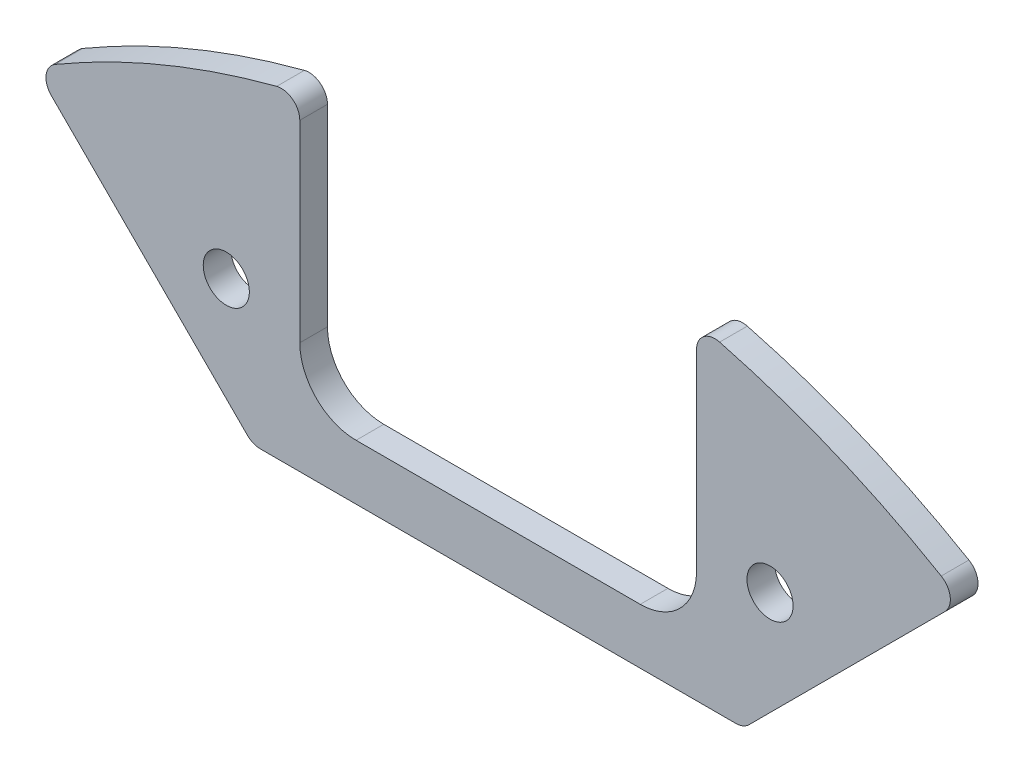
SolidWorks part; units mm, degrees
material "5052-H34"
ref_plane "正面" through (0, 0, 0) normal (0, 0, 1) x (1, 0, 0)
ref_plane "平面" through (0, 0, 0) normal (0, 1, 0) x (1, 0, 0)
ref_plane "右側面" through (0, 0, 0) normal (1, 0, 0) x (0, 0, -1)
sketch "ｽｹｯﾁ1" plane through (0, 0, 0) normal (0, 0, 1) x (1, 0, 0)
  circle A0 centre (0, 0) radius 47.5
  dimension "D1" = 95
extrude "ﾎﾞｽ - 押し出し1" add sketch "ｽｹｯﾁ1" along normal blind 1.5
sketch "ｽｹｯﾁ2" plane through (0, 0, 1.5) normal (0, 0, 1) x (1, 0, 0)
  line L0 (0, 0) -> (0, 47.5) construction
  line L1 (-10.75, 43.525) -> (-10.75, 52.5)
  line L2 (-10.75, 31.5) -> (10.75, 31.5)
  line L3 (-10.75, 31.5) -> (-10.75, 40.475)
  line L4 (-10.75, 52.5) -> (10.75, 52.5)
  line L5 (10.75, 31.5) -> (10.75, 40.475)
  line L6 (-10.75, 31.5) -> (10.75, 52.5) construction
  line L7 (-10.75, 52.5) -> (10.75, 31.5) construction
  line L8 (-13, 43.525) -> (-10.75, 43.525)
  line L9 (-13, 43.525) -> (-13, 40.475)
  line L10 (-13, 40.475) -> (-10.75, 40.475)
  line L11 (13, 43.525) -> (13, 40.475)
  line L12 (-13, 43.525) -> (13, 40.475) construction
  line L13 (-13, 40.475) -> (13, 43.525) construction
  line L14 (10.75, 43.525) -> (10.75, 52.5)
  line L15 (10.75, 43.525) -> (13, 43.525)
  line L17 (10.75, 40.475) -> (13, 40.475)
  circle A0 centre (0, 0) radius 47.5 construction
  point P5 (0, 42)
  point P10 (0, 42)
  dimension "D1" = 42
  dimension "D2" = 21.5
  dimension "D3" = 21
  dimension "D4" = 3.05
  dimension "D5" = 26
extrude "ｶｯﾄ - 押し出し1" cut sketch "ｽｹｯﾁ2" against normal through all
sketch "ｽｹｯﾁ3" plane through (0, 0, 1.5) normal (0, 0, 1) x (1, 0, 0)
  line L1 (-8.8388, -8.8388) -> (8.8388, -8.8388) construction
  line L2 (-8.8388, -8.8388) -> (-8.8388, 8.8388) construction
  line L3 (-8.8388, 8.8388) -> (8.8388, 8.8388) construction
  line L4 (8.8388, -8.8388) -> (8.8388, 8.8388) construction
  line L5 (-8.8388, -8.8388) -> (8.8388, 8.8388) construction
  line L6 (-8.8388, 8.8388) -> (8.8388, -8.8388) construction
  circle A0 centre (0, 0) radius 3.1
  circle A1 centre (0, 0) radius 6.5 construction
  circle A2 centre (0, 6.5) radius 1.6
  circle A3 centre (6.5, 0) radius 1.6
  circle A4 centre (0, -6.5) radius 1.6
  circle A5 centre (-6.5, 0) radius 1.6
  circle A6 centre (0, 0) radius 12.5 construction
  circle A7 centre (8.8388, 8.8388) radius 1.6
  circle A8 centre (8.8388, -8.8388) radius 1.6
  circle A9 centre (-8.8388, -8.8388) radius 1.6
  circle A10 centre (-8.8388, 8.8388) radius 1.6
  dimension "D1" = 6.2
  dimension "D2" = 13
  dimension "D3" = 3.2
  dimension "D5" = 25
  dimension "D6" = 3.2
  dimension "D4" = 4
  dimension "D7" = 4
extrude "ｶｯﾄ - 押し出し2" cut sketch "ｽｹｯﾁ3" against normal through all and the other way through all
sketch "ｽｹｯﾁ4" plane through (0, 0, 1.5) normal (0, 0, 1) x (1, 0, 0)
  line L0 (0, 31.5) -> (0, 0) construction
  line L1 (-10.75, 31.5) -> (10.75, 31.5) construction
  line L2 (0, 0) -> (14.7333, 35.5694) construction
  circle A0 centre (0, 0) radius 22.5 construction
  circle A1 centre (0, 0) radius 38.5 construction
  circle A2 centre (14.7333, 35.5694) radius 1.25
  circle A3 centre (8.6104, 20.7873) radius 1.25
  dimension "D1" = 45
  dimension "D2" = 77
  dimension "D4" = 2.5
  dimension "D3" = 22.5
extrude "ｶｯﾄ - 押し出し3" cut sketch "ｽｹｯﾁ4" against normal through all
sketch "ｽｹｯﾁ5" plane through (0, 0, 1.5) normal (0, 0, 1) x (1, 0, 0)
  line L0 (0, 0) -> (14.7333, 35.5694) construction
  line L1 (-10.75, 31.5) -> (10.75, 31.5) construction
  line L2 (-10.75, 31.5) -> (10.75, 31.5) construction
  line L3 (-7.1883, 26.5) -> (7.1883, 26.5)
  line L4 (-3.3281, 17.1806) -> (-7.1883, 26.5)
  line L5 (0, 31.5) -> (0, 0) construction
  line L6 (-10.75, 26.5) -> (10.75, 26.5) construction
  line L9 (-3.3281, 17.1806) -> (3.3281, 17.1806)
  line L10 (3.3281, 17.1806) -> (7.1883, 26.5)
  circle A0 centre (0, 0) radius 17.5 construction
  dimension "D3" = 35
  dimension "D2" = 7
  dimension "D1" = 5
extrude "ｶｯﾄ - 押し出し4" cut sketch "ｽｹｯﾁ5" against normal through all and the other way through all
fillet "ﾌｨﾚｯﾄ1" radius 1 6 edges at (-3.3281, 17.1806, 0.75) (3.3281, 17.1806, 0.75) (7.1883, 26.5, 0.75) (-7.1883, 26.5, 0.75) (10.75, 46.2676, 0.75) (-10.75, 46.2676, 0.75)
fillet "ﾌｨﾚｯﾄ2" radius 0.2 4 edges at (13, 43.525, 0.75) (13, 40.475, 0.75) (-13, 43.525, 0.75) (-13, 40.475, 0.75)
fillet "ﾌｨﾚｯﾄ3" radius 3.05 2 edges at (10.75, 31.5, 0.75) (-10.75, 31.5, 0.75)
ref_axis "軸1" through (0, 0, 0) along (0, 0, 1)
pattern_circular "円形ﾊﾟﾀｰﾝ1" count 8 over 360 about axis through (0, 0, 0) along (0, 0, 1) of "ｶｯﾄ - 押し出し1", "ﾌｨﾚｯﾄ1", "ｶｯﾄ - 押し出し4", "ｶｯﾄ - 押し出し3", "ﾌｨﾚｯﾄ2", "ﾌｨﾚｯﾄ3"
sketch "ｽｹｯﾁ6" plane through (0, 0, 1.5) normal (0, 0, 1) x (1, 0, 0)
  line L0 (7.7, 28.5) -> (-7.7, 28.5)
  line L1 (-7.7, 28.5) -> (-13.2972, 28.5)
  line L2 (-13.2972, 28.5) -> (-21.0187, 36.2215)
  line L3 (7.7, 28.5) -> (13.2972, 28.5)
  line L4 (25.5973, 14.7078) -> (14.7078, 25.5973)
  line L7 (28.5, -7.7) -> (28.5, 7.7)
  line L10 (14.7078, -25.5973) -> (25.5973, -14.7078)
  line L13 (-7.7, -28.5) -> (7.7, -28.5)
  line L16 (-25.5973, -14.7078) -> (-14.7078, -25.5973)
  line L19 (-28.5, 7.7) -> (-28.5, -7.7)
  line L22 (-14.7078, 25.5973) -> (-25.5973, 14.7078)
  line L23 (13.2972, 28.5) -> (21.0187, 36.2215)
  line L88 (39.4148, 24.212) -> (38.3782, 23.1754)
  line L89 (38.3782, 23.1754) -> (39.8278, 21.7259)
  line L90 (39.8278, 21.443) -> (37.954, 19.5692)
  line L91 (37.6711, 19.5692) -> (36.2215, 21.0187)
  line L92 (36.2215, 21.0187) -> (32.0319, 16.8291)
  line L93 (27.7186, 16.8291) -> (16.8291, 27.7186)
  line L94 (16.8291, 32.0319) -> (21.0187, 36.2215)
  line L95 (21.0187, 36.2215) -> (19.5692, 37.6711)
  line L96 (19.5692, 37.954) -> (21.443, 39.8278)
  line L97 (21.7259, 39.8278) -> (23.1754, 38.3782)
  line L98 (23.1754, 38.3782) -> (24.212, 39.4148)
  line L99 (10.75, 44.991) -> (10.75, 43.525)
  line L100 (10.75, 43.525) -> (12.8, 43.525)
  line L101 (13, 43.325) -> (13, 40.675)
  line L102 (12.8, 40.475) -> (10.75, 40.475)
  line L103 (10.75, 40.475) -> (10.75, 34.55)
  line L104 (7.7, 31.5) -> (-7.7, 31.5)
  line L105 (-10.75, 34.55) -> (-10.75, 40.475)
  line L106 (-10.75, 40.475) -> (-12.8, 40.475)
  line L107 (-13, 40.675) -> (-13, 43.325)
  line L108 (-12.8, 43.525) -> (-10.75, 43.525)
  line L109 (-10.75, 43.525) -> (-10.75, 44.991)
  line L110 (-24.212, 39.4148) -> (-23.1754, 38.3782)
  line L111 (-23.1754, 38.3782) -> (-21.7259, 39.8278)
  line L112 (-21.443, 39.8278) -> (-19.5692, 37.954)
  line L113 (-19.5692, 37.6711) -> (-21.0187, 36.2215)
  line L114 (-21.0187, 36.2215) -> (-16.8291, 32.0319)
  line L115 (-16.8291, 27.7186) -> (-27.7186, 16.8291)
  line L116 (-32.0319, 16.8291) -> (-36.2215, 21.0187)
  line L117 (-36.2215, 21.0187) -> (-37.6711, 19.5692)
  line L118 (-37.954, 19.5692) -> (-39.8278, 21.443)
  line L119 (-39.8278, 21.7259) -> (-38.3782, 23.1754)
  line L120 (-38.3782, 23.1754) -> (-39.4148, 24.212)
  line L121 (-44.991, 10.75) -> (-43.525, 10.75)
  line L122 (-43.525, 10.75) -> (-43.525, 12.8)
  line L123 (-43.325, 13) -> (-40.675, 13)
  line L124 (-40.475, 12.8) -> (-40.475, 10.75)
  line L125 (-40.475, 10.75) -> (-34.55, 10.75)
  line L126 (-31.5, 7.7) -> (-31.5, -7.7)
  line L127 (-34.55, -10.75) -> (-40.475, -10.75)
  line L128 (-40.475, -10.75) -> (-40.475, -12.8)
  line L129 (-40.675, -13) -> (-43.325, -13)
  line L130 (-43.525, -12.8) -> (-43.525, -10.75)
  line L131 (-43.525, -10.75) -> (-44.991, -10.75)
  line L132 (-39.4148, -24.212) -> (-38.3782, -23.1754)
  line L133 (-38.3782, -23.1754) -> (-39.8278, -21.7259)
  line L134 (-39.8278, -21.443) -> (-37.954, -19.5692)
  line L135 (-37.6711, -19.5692) -> (-36.2215, -21.0187)
  line L136 (-36.2215, -21.0187) -> (-32.0319, -16.8291)
  line L137 (-27.7186, -16.8291) -> (-16.8291, -27.7186)
  line L138 (-16.8291, -32.0319) -> (-21.0187, -36.2215)
  line L139 (-21.0187, -36.2215) -> (-19.5692, -37.6711)
  line L140 (-19.5692, -37.954) -> (-21.443, -39.8278)
  line L141 (-21.7259, -39.8278) -> (-23.1754, -38.3782)
  line L142 (-23.1754, -38.3782) -> (-24.212, -39.4148)
  line L143 (-10.75, -44.991) -> (-10.75, -43.525)
  line L144 (-10.75, -43.525) -> (-12.8, -43.525)
  line L145 (-13, -43.325) -> (-13, -40.675)
  line L146 (-12.8, -40.475) -> (-10.75, -40.475)
  line L147 (-10.75, -40.475) -> (-10.75, -34.55)
  line L148 (-7.7, -31.5) -> (7.7, -31.5)
  line L149 (10.75, -34.55) -> (10.75, -40.475)
  line L150 (10.75, -40.475) -> (12.8, -40.475)
  line L151 (13, -40.675) -> (13, -43.325)
  line L152 (12.8, -43.525) -> (10.75, -43.525)
  line L153 (10.75, -43.525) -> (10.75, -44.991)
  line L154 (24.212, -39.4148) -> (23.1754, -38.3782)
  line L155 (23.1754, -38.3782) -> (21.7259, -39.8278)
  line L156 (21.443, -39.8278) -> (19.5692, -37.954)
  line L157 (19.5692, -37.6711) -> (21.0187, -36.2215)
  line L158 (21.0187, -36.2215) -> (16.8291, -32.0319)
  line L159 (16.8291, -27.7186) -> (27.7186, -16.8291)
  line L160 (32.0319, -16.8291) -> (36.2215, -21.0187)
  line L161 (36.2215, -21.0187) -> (37.6711, -19.5692)
  line L162 (37.954, -19.5692) -> (39.8278, -21.443)
  line L163 (39.8278, -21.7259) -> (38.3782, -23.1754)
  line L164 (38.3782, -23.1754) -> (39.4148, -24.212)
  line L165 (44.991, -10.75) -> (43.525, -10.75)
  line L166 (43.525, -10.75) -> (43.525, -12.8)
  line L167 (43.325, -13) -> (40.675, -13)
  line L168 (40.475, -12.8) -> (40.475, -10.75)
  line L169 (40.475, -10.75) -> (34.55, -10.75)
  line L170 (31.5, -7.7) -> (31.5, 7.7)
  line L171 (34.55, 10.75) -> (40.475, 10.75)
  line L172 (40.475, 10.75) -> (40.475, 12.8)
  line L173 (40.675, 13) -> (43.325, 13)
  line L174 (43.525, 12.8) -> (43.525, 10.75)
  line L175 (43.525, 10.75) -> (44.991, 10.75)
  line L176 (39.4148, 24.212) -> (38.3782, 23.1754)
  line L177 (38.3782, 23.1754) -> (39.8278, 21.7259)
  line L178 (39.8278, 21.443) -> (37.954, 19.5692)
  line L179 (37.6711, 19.5692) -> (36.2215, 21.0187)
  line L180 (36.2215, 21.0187) -> (32.0319, 16.8291)
  line L181 (27.7186, 16.8291) -> (16.8291, 27.7186)
  line L182 (16.8291, 32.0319) -> (21.0187, 36.2215)
  line L183 (21.0187, 36.2215) -> (19.5692, 37.6711)
  line L184 (19.5692, 37.954) -> (21.443, 39.8278)
  line L185 (21.7259, 39.8278) -> (23.1754, 38.3782)
  line L186 (23.1754, 38.3782) -> (24.212, 39.4148)
  line L187 (10.75, 44.991) -> (10.75, 43.525)
  line L188 (10.75, 43.525) -> (12.8, 43.525)
  line L189 (13, 43.325) -> (13, 40.675)
  line L190 (12.8, 40.475) -> (10.75, 40.475)
  line L191 (10.75, 40.475) -> (10.75, 34.55)
  line L192 (7.7, 31.5) -> (-7.7, 31.5)
  line L193 (-10.75, 34.55) -> (-10.75, 40.475)
  line L194 (-10.75, 40.475) -> (-12.8, 40.475)
  line L195 (-13, 40.675) -> (-13, 43.325)
  line L196 (-12.8, 43.525) -> (-10.75, 43.525)
  line L197 (-10.75, 43.525) -> (-10.75, 44.991)
  line L198 (-24.212, 39.4148) -> (-23.1754, 38.3782)
  line L199 (-23.1754, 38.3782) -> (-21.7259, 39.8278)
  line L200 (-21.443, 39.8278) -> (-19.5692, 37.954)
  line L201 (-19.5692, 37.6711) -> (-21.0187, 36.2215)
  line L202 (-21.0187, 36.2215) -> (-16.8291, 32.0319)
  line L203 (-16.8291, 27.7186) -> (-27.7186, 16.8291)
  line L204 (-32.0319, 16.8291) -> (-36.2215, 21.0187)
  line L205 (-36.2215, 21.0187) -> (-37.6711, 19.5692)
  line L206 (-37.954, 19.5692) -> (-39.8278, 21.443)
  line L207 (-39.8278, 21.7259) -> (-38.3782, 23.1754)
  line L208 (-38.3782, 23.1754) -> (-39.4148, 24.212)
  line L209 (-44.991, 10.75) -> (-43.525, 10.75)
  line L210 (-43.525, 10.75) -> (-43.525, 12.8)
  line L211 (-43.325, 13) -> (-40.675, 13)
  line L212 (-40.475, 12.8) -> (-40.475, 10.75)
  line L213 (-40.475, 10.75) -> (-34.55, 10.75)
  line L214 (-31.5, 7.7) -> (-31.5, -7.7)
  line L215 (-34.55, -10.75) -> (-40.475, -10.75)
  line L216 (-40.475, -10.75) -> (-40.475, -12.8)
  line L217 (-40.675, -13) -> (-43.325, -13)
  line L218 (-43.525, -12.8) -> (-43.525, -10.75)
  line L219 (-43.525, -10.75) -> (-44.991, -10.75)
  line L220 (-39.4148, -24.212) -> (-38.3782, -23.1754)
  line L221 (-38.3782, -23.1754) -> (-39.8278, -21.7259)
  line L222 (-39.8278, -21.443) -> (-37.954, -19.5692)
  line L223 (-37.6711, -19.5692) -> (-36.2215, -21.0187)
  line L224 (-36.2215, -21.0187) -> (-32.0319, -16.8291)
  line L225 (-27.7186, -16.8291) -> (-16.8291, -27.7186)
  line L226 (-16.8291, -32.0319) -> (-21.0187, -36.2215)
  line L227 (-21.0187, -36.2215) -> (-19.5692, -37.6711)
  line L228 (-19.5692, -37.954) -> (-21.443, -39.8278)
  line L229 (-21.7259, -39.8278) -> (-23.1754, -38.3782)
  line L230 (-23.1754, -38.3782) -> (-24.212, -39.4148)
  line L231 (-10.75, -44.991) -> (-10.75, -43.525)
  line L232 (-10.75, -43.525) -> (-12.8, -43.525)
  line L233 (-13, -43.325) -> (-13, -40.675)
  line L234 (-12.8, -40.475) -> (-10.75, -40.475)
  line L235 (-10.75, -40.475) -> (-10.75, -34.55)
  line L236 (-7.7, -31.5) -> (7.7, -31.5)
  line L237 (10.75, -34.55) -> (10.75, -40.475)
  line L238 (10.75, -40.475) -> (12.8, -40.475)
  line L239 (13, -40.675) -> (13, -43.325)
  line L240 (12.8, -43.525) -> (10.75, -43.525)
  line L241 (10.75, -43.525) -> (10.75, -44.991)
  line L242 (24.212, -39.4148) -> (23.1754, -38.3782)
  line L243 (23.1754, -38.3782) -> (21.7259, -39.8278)
  line L244 (21.443, -39.8278) -> (19.5692, -37.954)
  line L245 (19.5692, -37.6711) -> (21.0187, -36.2215)
  line L246 (21.0187, -36.2215) -> (16.8291, -32.0319)
  line L247 (16.8291, -27.7186) -> (27.7186, -16.8291)
  line L248 (32.0319, -16.8291) -> (36.2215, -21.0187)
  line L249 (36.2215, -21.0187) -> (37.6711, -19.5692)
  line L250 (37.954, -19.5692) -> (39.8278, -21.443)
  line L251 (39.8278, -21.7259) -> (38.3782, -23.1754)
  line L252 (38.3782, -23.1754) -> (39.4148, -24.212)
  line L253 (44.991, -10.75) -> (43.525, -10.75)
  line L254 (43.525, -10.75) -> (43.525, -12.8)
  line L255 (43.325, -13) -> (40.675, -13)
  line L256 (40.475, -12.8) -> (40.475, -10.75)
  line L257 (40.475, -10.75) -> (34.55, -10.75)
  line L258 (31.5, -7.7) -> (31.5, 7.7)
  line L259 (34.55, 10.75) -> (40.475, 10.75)
  line L260 (40.475, 10.75) -> (40.475, 12.8)
  line L261 (40.675, 13) -> (43.325, 13)
  line L262 (43.525, 12.8) -> (43.525, 10.75)
  line L263 (43.525, 10.75) -> (44.991, 10.75)
  arc A72 (45.9585, 12.0027) -> (40.9848, 24.0104) centre (0, 0) ccw
  arc A73 (40.9848, 24.0104) -> (39.4148, 24.212) centre (40.1219, 23.5049) ccw
  arc A74 (39.8278, 21.443) -> (39.8278, 21.7259) centre (39.6864, 21.5844) ccw
  arc A75 (37.6711, 19.5692) -> (37.954, 19.5692) centre (37.8125, 19.7106) ccw
  arc A76 (27.7186, 16.8291) -> (32.0319, 16.8291) centre (29.8753, 18.9858) ccw
  arc A77 (16.8291, 32.0319) -> (16.8291, 27.7186) centre (18.9858, 29.8753) ccw
  arc A78 (19.5692, 37.954) -> (19.5692, 37.6711) centre (19.7106, 37.8125) ccw
  arc A79 (21.7259, 39.8278) -> (21.443, 39.8278) centre (21.5844, 39.6864) ccw
  arc A80 (24.212, 39.4148) -> (24.0104, 40.9848) centre (23.5049, 40.1219) ccw
  arc A81 (24.0104, 40.9848) -> (12.0027, 45.9585) centre (0, 0) ccw
  arc A82 (12.0027, 45.9585) -> (10.75, 44.991) centre (11.75, 44.991) ccw
  arc A83 (13, 43.325) -> (12.8, 43.525) centre (12.8, 43.325) ccw
  arc A84 (12.8, 40.475) -> (13, 40.675) centre (12.8, 40.675) ccw
  arc A85 (7.7, 31.5) -> (10.75, 34.55) centre (7.7, 34.55) ccw
  arc A86 (-10.75, 34.55) -> (-7.7, 31.5) centre (-7.7, 34.55) ccw
  arc A87 (-13, 40.675) -> (-12.8, 40.475) centre (-12.8, 40.675) ccw
  arc A88 (-12.8, 43.525) -> (-13, 43.325) centre (-12.8, 43.325) ccw
  arc A89 (-10.75, 44.991) -> (-12.0027, 45.9585) centre (-11.75, 44.991) ccw
  arc A90 (-12.0027, 45.9585) -> (-24.0104, 40.9848) centre (0, 0) ccw
  arc A91 (-24.0104, 40.9848) -> (-24.212, 39.4148) centre (-23.5049, 40.1219) ccw
  arc A92 (-21.443, 39.8278) -> (-21.7259, 39.8278) centre (-21.5844, 39.6864) ccw
  arc A93 (-19.5692, 37.6711) -> (-19.5692, 37.954) centre (-19.7106, 37.8125) ccw
  arc A94 (-16.8291, 27.7186) -> (-16.8291, 32.0319) centre (-18.9858, 29.8753) ccw
  arc A95 (-32.0319, 16.8291) -> (-27.7186, 16.8291) centre (-29.8753, 18.9858) ccw
  arc A96 (-37.954, 19.5692) -> (-37.6711, 19.5692) centre (-37.8125, 19.7106) ccw
  arc A97 (-39.8278, 21.7259) -> (-39.8278, 21.443) centre (-39.6864, 21.5844) ccw
  arc A98 (-39.4148, 24.212) -> (-40.9848, 24.0104) centre (-40.1219, 23.5049) ccw
  arc A99 (-40.9848, 24.0104) -> (-45.9585, 12.0027) centre (0, 0) ccw
  arc A100 (-45.9585, 12.0027) -> (-44.991, 10.75) centre (-44.991, 11.75) ccw
  arc A101 (-43.325, 13) -> (-43.525, 12.8) centre (-43.325, 12.8) ccw
  arc A102 (-40.475, 12.8) -> (-40.675, 13) centre (-40.675, 12.8) ccw
  arc A103 (-31.5, 7.7) -> (-34.55, 10.75) centre (-34.55, 7.7) ccw
  arc A104 (-34.55, -10.75) -> (-31.5, -7.7) centre (-34.55, -7.7) ccw
  arc A105 (-40.675, -13) -> (-40.475, -12.8) centre (-40.675, -12.8) ccw
  arc A106 (-43.525, -12.8) -> (-43.325, -13) centre (-43.325, -12.8) ccw
  arc A107 (-44.991, -10.75) -> (-45.9585, -12.0027) centre (-44.991, -11.75) ccw
  arc A108 (-45.9585, -12.0027) -> (-40.9848, -24.0104) centre (0, 0) ccw
  arc A109 (-40.9848, -24.0104) -> (-39.4148, -24.212) centre (-40.1219, -23.5049) ccw
  arc A110 (-39.8278, -21.443) -> (-39.8278, -21.7259) centre (-39.6864, -21.5844) ccw
  arc A111 (-37.6711, -19.5692) -> (-37.954, -19.5692) centre (-37.8125, -19.7106) ccw
  arc A112 (-27.7186, -16.8291) -> (-32.0319, -16.8291) centre (-29.8753, -18.9858) ccw
  arc A113 (-16.8291, -32.0319) -> (-16.8291, -27.7186) centre (-18.9858, -29.8753) ccw
  arc A114 (-19.5692, -37.954) -> (-19.5692, -37.6711) centre (-19.7106, -37.8125) ccw
  arc A115 (-21.7259, -39.8278) -> (-21.443, -39.8278) centre (-21.5844, -39.6864) ccw
  arc A116 (-24.212, -39.4148) -> (-24.0104, -40.9848) centre (-23.5049, -40.1219) ccw
  arc A117 (-24.0104, -40.9848) -> (-12.0027, -45.9585) centre (0, 0) ccw
  arc A118 (-12.0027, -45.9585) -> (-10.75, -44.991) centre (-11.75, -44.991) ccw
  arc A119 (-13, -43.325) -> (-12.8, -43.525) centre (-12.8, -43.325) ccw
  arc A120 (-12.8, -40.475) -> (-13, -40.675) centre (-12.8, -40.675) ccw
  arc A121 (-7.7, -31.5) -> (-10.75, -34.55) centre (-7.7, -34.55) ccw
  arc A122 (10.75, -34.55) -> (7.7, -31.5) centre (7.7, -34.55) ccw
  arc A123 (13, -40.675) -> (12.8, -40.475) centre (12.8, -40.675) ccw
  arc A124 (12.8, -43.525) -> (13, -43.325) centre (12.8, -43.325) ccw
  arc A125 (10.75, -44.991) -> (12.0027, -45.9585) centre (11.75, -44.991) ccw
  arc A126 (12.0027, -45.9585) -> (24.0104, -40.9848) centre (0, 0) ccw
  arc A127 (24.0104, -40.9848) -> (24.212, -39.4148) centre (23.5049, -40.1219) ccw
  arc A128 (21.443, -39.8278) -> (21.7259, -39.8278) centre (21.5844, -39.6864) ccw
  arc A129 (19.5692, -37.6711) -> (19.5692, -37.954) centre (19.7106, -37.8125) ccw
  arc A130 (16.8291, -27.7186) -> (16.8291, -32.0319) centre (18.9858, -29.8753) ccw
  arc A131 (32.0319, -16.8291) -> (27.7186, -16.8291) centre (29.8753, -18.9858) ccw
  arc A132 (37.954, -19.5692) -> (37.6711, -19.5692) centre (37.8125, -19.7106) ccw
  arc A133 (39.8278, -21.7259) -> (39.8278, -21.443) centre (39.6864, -21.5844) ccw
  arc A134 (39.4148, -24.212) -> (40.9848, -24.0104) centre (40.1219, -23.5049) ccw
  arc A135 (40.9848, -24.0104) -> (45.9585, -12.0027) centre (0, 0) ccw
  arc A136 (45.9585, -12.0027) -> (44.991, -10.75) centre (44.991, -11.75) ccw
  arc A137 (43.325, -13) -> (43.525, -12.8) centre (43.325, -12.8) ccw
  arc A138 (40.475, -12.8) -> (40.675, -13) centre (40.675, -12.8) ccw
  arc A139 (31.5, -7.7) -> (34.55, -10.75) centre (34.55, -7.7) ccw
  arc A140 (34.55, 10.75) -> (31.5, 7.7) centre (34.55, 7.7) ccw
  arc A141 (40.675, 13) -> (40.475, 12.8) centre (40.675, 12.8) ccw
  arc A142 (43.525, 12.8) -> (43.325, 13) centre (43.325, 12.8) ccw
  arc A143 (44.991, 10.75) -> (45.9585, 12.0027) centre (44.991, 11.75) ccw
  arc A144 (45.9585, 12.0027) -> (40.9848, 24.0104) centre (0, 0) ccw
  arc A145 (40.9848, 24.0104) -> (39.4148, 24.212) centre (40.1219, 23.5049) ccw
  arc A146 (39.8278, 21.443) -> (39.8278, 21.7259) centre (39.6864, 21.5844) ccw
  arc A147 (37.6711, 19.5692) -> (37.954, 19.5692) centre (37.8125, 19.7106) ccw
  arc A148 (27.7186, 16.8291) -> (32.0319, 16.8291) centre (29.8753, 18.9858) ccw
  arc A149 (16.8291, 32.0319) -> (16.8291, 27.7186) centre (18.9858, 29.8753) ccw
  arc A150 (19.5692, 37.954) -> (19.5692, 37.6711) centre (19.7106, 37.8125) ccw
  arc A151 (21.7259, 39.8278) -> (21.443, 39.8278) centre (21.5844, 39.6864) ccw
  arc A152 (24.212, 39.4148) -> (24.0104, 40.9848) centre (23.5049, 40.1219) ccw
  arc A153 (24.0104, 40.9848) -> (12.0027, 45.9585) centre (0, 0) ccw
  arc A154 (12.0027, 45.9585) -> (10.75, 44.991) centre (11.75, 44.991) ccw
  arc A155 (13, 43.325) -> (12.8, 43.525) centre (12.8, 43.325) ccw
  arc A156 (12.8, 40.475) -> (13, 40.675) centre (12.8, 40.675) ccw
  arc A157 (7.7, 31.5) -> (10.75, 34.55) centre (7.7, 34.55) ccw
  arc A158 (-10.75, 34.55) -> (-7.7, 31.5) centre (-7.7, 34.55) ccw
  arc A159 (-13, 40.675) -> (-12.8, 40.475) centre (-12.8, 40.675) ccw
  arc A160 (-12.8, 43.525) -> (-13, 43.325) centre (-12.8, 43.325) ccw
  arc A161 (-10.75, 44.991) -> (-12.0027, 45.9585) centre (-11.75, 44.991) ccw
  arc A162 (-12.0027, 45.9585) -> (-24.0104, 40.9848) centre (0, 0) ccw
  arc A163 (-24.0104, 40.9848) -> (-24.212, 39.4148) centre (-23.5049, 40.1219) ccw
  arc A164 (-21.443, 39.8278) -> (-21.7259, 39.8278) centre (-21.5844, 39.6864) ccw
  arc A165 (-19.5692, 37.6711) -> (-19.5692, 37.954) centre (-19.7106, 37.8125) ccw
  arc A166 (-16.8291, 27.7186) -> (-16.8291, 32.0319) centre (-18.9858, 29.8753) ccw
  arc A167 (-32.0319, 16.8291) -> (-27.7186, 16.8291) centre (-29.8753, 18.9858) ccw
  arc A168 (-37.954, 19.5692) -> (-37.6711, 19.5692) centre (-37.8125, 19.7106) ccw
  arc A169 (-39.8278, 21.7259) -> (-39.8278, 21.443) centre (-39.6864, 21.5844) ccw
  arc A170 (-39.4148, 24.212) -> (-40.9848, 24.0104) centre (-40.1219, 23.5049) ccw
  arc A171 (-40.9848, 24.0104) -> (-45.9585, 12.0027) centre (0, 0) ccw
  arc A172 (-45.9585, 12.0027) -> (-44.991, 10.75) centre (-44.991, 11.75) ccw
  arc A173 (-43.325, 13) -> (-43.525, 12.8) centre (-43.325, 12.8) ccw
  arc A174 (-40.475, 12.8) -> (-40.675, 13) centre (-40.675, 12.8) ccw
  arc A175 (-31.5, 7.7) -> (-34.55, 10.75) centre (-34.55, 7.7) ccw
  arc A176 (-34.55, -10.75) -> (-31.5, -7.7) centre (-34.55, -7.7) ccw
  arc A177 (-40.675, -13) -> (-40.475, -12.8) centre (-40.675, -12.8) ccw
  arc A178 (-43.525, -12.8) -> (-43.325, -13) centre (-43.325, -12.8) ccw
  arc A179 (-44.991, -10.75) -> (-45.9585, -12.0027) centre (-44.991, -11.75) ccw
  arc A180 (-45.9585, -12.0027) -> (-40.9848, -24.0104) centre (0, 0) ccw
  arc A181 (-40.9848, -24.0104) -> (-39.4148, -24.212) centre (-40.1219, -23.5049) ccw
  arc A182 (-39.8278, -21.443) -> (-39.8278, -21.7259) centre (-39.6864, -21.5844) ccw
  arc A183 (-37.6711, -19.5692) -> (-37.954, -19.5692) centre (-37.8125, -19.7106) ccw
  arc A184 (-27.7186, -16.8291) -> (-32.0319, -16.8291) centre (-29.8753, -18.9858) ccw
  arc A185 (-16.8291, -32.0319) -> (-16.8291, -27.7186) centre (-18.9858, -29.8753) ccw
  arc A186 (-19.5692, -37.954) -> (-19.5692, -37.6711) centre (-19.7106, -37.8125) ccw
  arc A187 (-21.7259, -39.8278) -> (-21.443, -39.8278) centre (-21.5844, -39.6864) ccw
  arc A188 (-24.212, -39.4148) -> (-24.0104, -40.9848) centre (-23.5049, -40.1219) ccw
  arc A189 (-24.0104, -40.9848) -> (-12.0027, -45.9585) centre (0, 0) ccw
  arc A190 (-12.0027, -45.9585) -> (-10.75, -44.991) centre (-11.75, -44.991) ccw
  arc A191 (-13, -43.325) -> (-12.8, -43.525) centre (-12.8, -43.325) ccw
  arc A192 (-12.8, -40.475) -> (-13, -40.675) centre (-12.8, -40.675) ccw
  arc A193 (-7.7, -31.5) -> (-10.75, -34.55) centre (-7.7, -34.55) ccw
  arc A194 (10.75, -34.55) -> (7.7, -31.5) centre (7.7, -34.55) ccw
  arc A195 (13, -40.675) -> (12.8, -40.475) centre (12.8, -40.675) ccw
  arc A196 (12.8, -43.525) -> (13, -43.325) centre (12.8, -43.325) ccw
  arc A197 (10.75, -44.991) -> (12.0027, -45.9585) centre (11.75, -44.991) ccw
  arc A198 (12.0027, -45.9585) -> (24.0104, -40.9848) centre (0, 0) ccw
  arc A199 (24.0104, -40.9848) -> (24.212, -39.4148) centre (23.5049, -40.1219) ccw
  arc A200 (21.443, -39.8278) -> (21.7259, -39.8278) centre (21.5844, -39.6864) ccw
  arc A201 (19.5692, -37.6711) -> (19.5692, -37.954) centre (19.7106, -37.8125) ccw
  arc A202 (16.8291, -27.7186) -> (16.8291, -32.0319) centre (18.9858, -29.8753) ccw
  arc A203 (32.0319, -16.8291) -> (27.7186, -16.8291) centre (29.8753, -18.9858) ccw
  arc A204 (37.954, -19.5692) -> (37.6711, -19.5692) centre (37.8125, -19.7106) ccw
  arc A205 (39.8278, -21.7259) -> (39.8278, -21.443) centre (39.6864, -21.5844) ccw
  arc A206 (39.4148, -24.212) -> (40.9848, -24.0104) centre (40.1219, -23.5049) ccw
  arc A207 (40.9848, -24.0104) -> (45.9585, -12.0027) centre (0, 0) ccw
  arc A208 (45.9585, -12.0027) -> (44.991, -10.75) centre (44.991, -11.75) ccw
  arc A209 (43.325, -13) -> (43.525, -12.8) centre (43.325, -12.8) ccw
  arc A210 (40.475, -12.8) -> (40.675, -13) centre (40.675, -12.8) ccw
  arc A211 (31.5, -7.7) -> (34.55, -10.75) centre (34.55, -7.7) ccw
  arc A212 (34.55, 10.75) -> (31.5, 7.7) centre (34.55, 7.7) ccw
  arc A213 (40.675, 13) -> (40.475, 12.8) centre (40.675, 12.8) ccw
  arc A214 (43.525, 12.8) -> (43.325, 13) centre (43.325, 12.8) ccw
  arc A215 (44.991, 10.75) -> (45.9585, 12.0027) centre (44.991, 11.75) ccw
  dimension "D4" = 3
  dimension "D5" = 3
  dimension "D1" = 0
  dimension "D2" = 3
  dimension "D3" = 8
extrude "ｶｯﾄ - 押し出し5" cut sketch "ｽｹｯﾁ6" against normal through all contours L22 L19 L16 L13 L10 L7 L4 L0 region at (0, -3.0739, 1.5)
sketch "ｽｹｯﾁ7" plane through (0, 0, 1.5) normal (0, 0, 1) x (1, 0, 0)
  line L0 (-10.75, 43.525) -> (-10.75, 40.475)
  line L1 (10.75, 43.525) -> (10.75, 40.475)
  line L2 (23.1754, 38.3782) -> (21.0187, 36.2215)
  line L15 (-23.1754, 38.3782) -> (-21.0187, 36.2215)
  line L38 (-13.2972, 28.5) -> (13.2972, 28.5)
  line L39 (-13.2972, 28.5) -> (13.2972, 28.5)
  line L94 (13.2972, 28.5) -> (21.0187, 36.2215)
  line L95 (21.0187, 36.2215) -> (19.5692, 37.6711)
  line L96 (19.5692, 37.954) -> (21.443, 39.8278)
  line L97 (21.7259, 39.8278) -> (23.1754, 38.3782)
  line L98 (23.1754, 38.3782) -> (24.212, 39.4148)
  line L99 (10.75, 44.991) -> (10.75, 43.525)
  line L100 (10.75, 43.525) -> (12.8, 43.525)
  line L101 (13, 43.325) -> (13, 40.675)
  line L102 (12.8, 40.475) -> (10.75, 40.475)
  line L103 (10.75, 40.475) -> (10.75, 34.55)
  line L104 (7.7, 31.5) -> (-7.7, 31.5)
  line L105 (-10.75, 34.55) -> (-10.75, 40.475)
  line L106 (-10.75, 40.475) -> (-12.8, 40.475)
  line L107 (-13, 40.675) -> (-13, 43.325)
  line L108 (-12.8, 43.525) -> (-10.75, 43.525)
  line L109 (-10.75, 43.525) -> (-10.75, 44.991)
  line L110 (-24.212, 39.4148) -> (-23.1754, 38.3782)
  line L111 (-23.1754, 38.3782) -> (-21.7259, 39.8278)
  line L112 (-21.443, 39.8278) -> (-19.5692, 37.954)
  line L113 (-19.5692, 37.6711) -> (-21.0187, 36.2215)
  line L114 (-21.0187, 36.2215) -> (-13.2972, 28.5)
  line L182 (13.2972, 28.5) -> (21.0187, 36.2215)
  line L183 (21.0187, 36.2215) -> (19.5692, 37.6711)
  line L184 (19.5692, 37.954) -> (21.443, 39.8278)
  line L185 (21.7259, 39.8278) -> (23.1754, 38.3782)
  line L186 (23.1754, 38.3782) -> (24.212, 39.4148)
  line L187 (10.75, 44.991) -> (10.75, 43.525)
  line L188 (10.75, 43.525) -> (12.8, 43.525)
  line L189 (13, 43.325) -> (13, 40.675)
  line L190 (12.8, 40.475) -> (10.75, 40.475)
  line L191 (10.75, 40.475) -> (10.75, 34.55)
  line L192 (7.7, 31.5) -> (-7.7, 31.5)
  line L193 (-10.75, 34.55) -> (-10.75, 40.475)
  line L194 (-10.75, 40.475) -> (-12.8, 40.475)
  line L195 (-13, 40.675) -> (-13, 43.325)
  line L196 (-12.8, 43.525) -> (-10.75, 43.525)
  line L197 (-10.75, 43.525) -> (-10.75, 44.991)
  line L198 (-24.212, 39.4148) -> (-23.1754, 38.3782)
  line L199 (-23.1754, 38.3782) -> (-21.7259, 39.8278)
  line L200 (-21.443, 39.8278) -> (-19.5692, 37.954)
  line L201 (-19.5692, 37.6711) -> (-21.0187, 36.2215)
  line L202 (-21.0187, 36.2215) -> (-13.2972, 28.5)
  line L203 (-38.3782, -23.1754) -> (-36.2215, -21.0187)
  line L204 (-43.525, -10.75) -> (-40.475, -10.75)
  line L205 (-43.525, 10.75) -> (-40.475, 10.75)
  line L206 (-38.3782, 23.1754) -> (-36.2215, 21.0187)
  line L207 (43.525, -10.75) -> (40.475, -10.75)
  line L208 (38.3782, -23.1754) -> (36.2215, -21.0187)
  line L209 (23.1754, -38.3782) -> (21.0187, -36.2215)
  line L210 (10.75, -43.525) -> (10.75, -40.475)
  line L211 (-10.75, -43.525) -> (-10.75, -40.475)
  line L212 (-23.1754, -38.3782) -> (-21.0187, -36.2215)
  line L213 (38.3782, 23.1754) -> (36.2215, 21.0187)
  line L214 (43.525, 10.75) -> (40.475, 10.75)
  arc A78 (19.5692, 37.954) -> (19.5692, 37.6711) centre (19.7106, 37.8125) ccw
  arc A79 (21.7259, 39.8278) -> (21.443, 39.8278) centre (21.5844, 39.6864) ccw
  arc A80 (24.212, 39.4148) -> (24.0104, 40.9848) centre (23.5049, 40.1219) ccw
  arc A81 (24.0104, 40.9848) -> (12.0027, 45.9585) centre (0, 0) ccw
  arc A82 (12.0027, 45.9585) -> (10.75, 44.991) centre (11.75, 44.991) ccw
  arc A83 (13, 43.325) -> (12.8, 43.525) centre (12.8, 43.325) ccw
  arc A84 (12.8, 40.475) -> (13, 40.675) centre (12.8, 40.675) ccw
  arc A85 (7.7, 31.5) -> (10.75, 34.55) centre (7.7, 34.55) ccw
  arc A86 (-10.75, 34.55) -> (-7.7, 31.5) centre (-7.7, 34.55) ccw
  arc A87 (-13, 40.675) -> (-12.8, 40.475) centre (-12.8, 40.675) ccw
  arc A88 (-12.8, 43.525) -> (-13, 43.325) centre (-12.8, 43.325) ccw
  arc A89 (-10.75, 44.991) -> (-12.0027, 45.9585) centre (-11.75, 44.991) ccw
  arc A90 (-12.0027, 45.9585) -> (-24.0104, 40.9848) centre (0, 0) ccw
  arc A91 (-24.0104, 40.9848) -> (-24.212, 39.4148) centre (-23.5049, 40.1219) ccw
  arc A92 (-21.443, 39.8278) -> (-21.7259, 39.8278) centre (-21.5844, 39.6864) ccw
  arc A93 (-19.5692, 37.6711) -> (-19.5692, 37.954) centre (-19.7106, 37.8125) ccw
  arc A150 (19.5692, 37.954) -> (19.5692, 37.6711) centre (19.7106, 37.8125) ccw
  arc A151 (21.7259, 39.8278) -> (21.443, 39.8278) centre (21.5844, 39.6864) ccw
  arc A152 (24.212, 39.4148) -> (24.0104, 40.9848) centre (23.5049, 40.1219) ccw
  arc A153 (24.0104, 40.9848) -> (12.0027, 45.9585) centre (0, 0) ccw
  arc A154 (12.0027, 45.9585) -> (10.75, 44.991) centre (11.75, 44.991) ccw
  arc A155 (13, 43.325) -> (12.8, 43.525) centre (12.8, 43.325) ccw
  arc A156 (12.8, 40.475) -> (13, 40.675) centre (12.8, 40.675) ccw
  arc A157 (7.7, 31.5) -> (10.75, 34.55) centre (7.7, 34.55) ccw
  arc A158 (-10.75, 34.55) -> (-7.7, 31.5) centre (-7.7, 34.55) ccw
  arc A159 (-13, 40.675) -> (-12.8, 40.475) centre (-12.8, 40.675) ccw
  arc A160 (-12.8, 43.525) -> (-13, 43.325) centre (-12.8, 43.325) ccw
  arc A161 (-10.75, 44.991) -> (-12.0027, 45.9585) centre (-11.75, 44.991) ccw
  arc A162 (-12.0027, 45.9585) -> (-24.0104, 40.9848) centre (0, 0) ccw
  arc A163 (-24.0104, 40.9848) -> (-24.212, 39.4148) centre (-23.5049, 40.1219) ccw
  arc A164 (-21.443, 39.8278) -> (-21.7259, 39.8278) centre (-21.5844, 39.6864) ccw
  arc A165 (-19.5692, 37.6711) -> (-19.5692, 37.954) centre (-19.7106, 37.8125) ccw
  line M340 (21.0187, 36.2215) -> (19.5692, 37.6711)
  arc M341 (19.5692, 37.6711) -> (19.5692, 37.954) centre (19.7106, 37.8125) cw
  line M342 (19.5692, 37.954) -> (21.443, 39.8278)
  arc M343 (21.443, 39.8278) -> (21.7259, 39.8278) centre (21.5844, 39.6864) cw
  line M344 (21.7259, 39.8278) -> (23.1754, 38.3782)
  line M370 (-23.1754, 38.3782) -> (-21.7259, 39.8278)
  arc M371 (-21.7259, 39.8278) -> (-21.443, 39.8278) centre (-21.5844, 39.6864) cw
  line M372 (-21.443, 39.8278) -> (-19.5692, 37.954)
  arc M373 (-19.5692, 37.954) -> (-19.5692, 37.6711) centre (-19.7106, 37.8125) cw
  line M374 (-19.5692, 37.6711) -> (-21.0187, 36.2215)
  dimension "D1" = 0
  dimension "D2" = 8
extrude "ﾎﾞｽ - 押し出し2" add sketch "ｽｹｯﾁ7" against normal blind 1.5 contours L196 A160 L195 A159 L194 L0 | L190 A156 L189 A155 L188 L1 | L15 M370 M374 M373 M372 M371 | L2 M344 M343 M342 M341 M340 region at (-11.8723, 42, 1.5) region at (-21.3035, 38.0935, 1.5) region at (11.8723, 42, 1.5) region at (21.3035, 38.0935, 1.5)
fillet "ﾌｨﾚｯﾄ4" radius 1 2 edges at (13.2972, 28.5, 0.75) (-13.2972, 28.5, 0.75)
